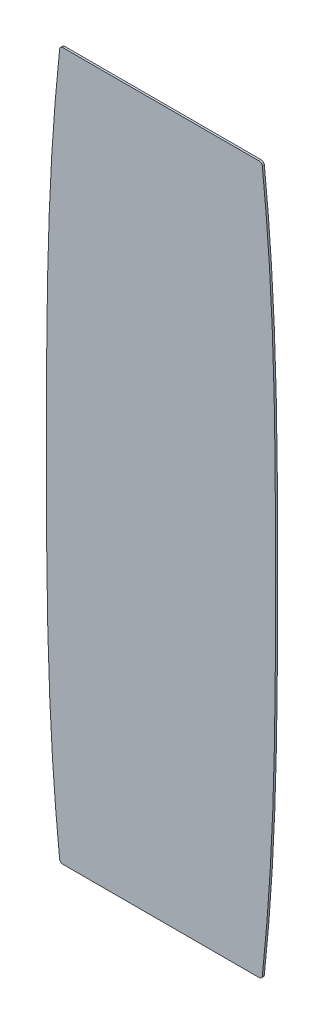
SolidWorks part; units mm, degrees
ref_plane "Front" through (0, 0, 0) normal (0, 0, 1) x (1, 0, 0)
ref_plane "Top" through (0, 0, 0) normal (0, 1, 0) x (1, 0, 0)
ref_plane "Right" through (0, 0, 0) normal (1, 0, 0) x (0, 0, -1)
sketch "Sketch1" plane through (0, 0, 0) normal (0, 0, 1) x (1, 0, 0)
  line L4 (-23.7959, -85.8) -> (23.7959, -85.8)
  line L5 (23.7959, 85.8) -> (-23.7959, 85.8)
  line L6 (-23.7959, -85.8) -> (23.7959, -85.8)
  line L7 (23.7959, 85.8) -> (-23.7959, 85.8)
  arc A8 (-24.5914, -85.0845) -> (-23.7959, -85.8) centre (-23.7959, -85) ccw
  arc A9 (23.7959, -85.8) -> (24.5914, -85.0845) centre (23.7959, -85) ccw
  arc A10 (24.5914, 85.0845) -> (23.7959, 85.8) centre (23.7959, 85) ccw
  arc A11 (-23.7959, 85.8) -> (-24.5914, 85.0845) centre (-23.7959, 85) ccw
  arc A12 (-24.5914, -85.0845) -> (-23.7959, -85.8) centre (-23.7959, -85) ccw
  arc A13 (23.7959, -85.8) -> (24.5914, -85.0845) centre (23.7959, -85) ccw
  arc A14 (24.5914, 85.0845) -> (23.7959, 85.8) centre (23.7959, 85) ccw
  arc A15 (-23.7959, 85.8) -> (-24.5914, 85.0845) centre (-23.7959, 85) ccw
  spline S8 degree 3 poles (-3802.0274, 987.7222) (80.8283, 660.6198) (-30.7141, 319.4581) (-27.6629, -28.4006) (-27.5516, -35.4997) (-27.1348, -49.6946) (-26.8273, -56.7856) (-26.1559, -67.4085) (-25.8975, -70.9473) (20.9467, -627.9264) (1017.3382, -1119.8071) (3591.242, -1509.4446) knots -11.748468 -11.748468 -11.748468 -11.748468 0.25 0.25 0.5 0.5 0.75 0.75 0.875 0.875 20.43848 20.43848 20.43848 20.43848 only from (-27.8, 0) to (-24.5914, -85.0845)
  spline S9 degree 3 poles (-3801.4835, -888.3345) (-433.1565, -789.8527) (2.3276, -444.1958) (26.8287, -56.7783) (27.1351, -49.686) (27.5518, -35.4924) (27.663, -28.3946) (30.7149, 319.6689) (-80.9395, 661.8598) (3808.3413, 961.2743) knots -13.168575 -13.168575 -13.168575 -13.168575 0.25 0.25 0.5 0.5 0.75 0.75 12.758606 12.758606 12.758606 12.758606 only from (24.5914, -85.0845) to (27.8, 0)
  spline S10 degree 3 poles (3802.0274, -987.7222) (-80.8283, -660.6198) (30.7141, -319.4581) (27.6629, 28.4006) (27.5516, 35.4997) (27.1348, 49.6946) (26.8273, 56.7856) (26.1559, 67.4085) (25.8975, 70.9473) (-20.9467, 627.9264) (-1017.3382, 1119.8071) (-3591.242, 1509.4446) knots -11.748468 -11.748468 -11.748468 -11.748468 0.25 0.25 0.5 0.5 0.75 0.75 0.875 0.875 20.43848 20.43848 20.43848 20.43848 only from (27.8, 0) to (24.5914, 85.0845)
  spline S11 degree 3 poles (3801.4835, 888.3345) (433.1565, 789.8527) (-2.3276, 444.1958) (-26.8287, 56.7783) (-27.1351, 49.686) (-27.5518, 35.4924) (-27.663, 28.3946) (-30.7149, -319.6689) (80.9395, -661.8598) (-3808.3413, -961.2743) knots -13.168575 -13.168575 -13.168575 -13.168575 0.25 0.25 0.5 0.5 0.75 0.75 12.758606 12.758606 12.758606 12.758606 only from (-24.5914, 85.0845) to (-27.8, 0)
  spline S12 degree 3 poles (-27.8, 0) (-27.8, -7.1003) (-27.7874, -14.2005) (-27.6629, -28.4006) (-27.5516, -35.4997) (-27.1348, -49.6946) (-26.8273, -56.7856) (-26.1559, -67.4085) (-25.8975, -70.9473) (-25.3027, -78.0197) (-24.9665, -81.5533) (-24.5914, -85.0845) knots 0 0 0 0 0.25 0.25 0.5 0.5 0.75 0.75 0.875 0.875 1 1 1 1
  spline S13 degree 3 poles (24.5914, -85.0845) (25.3415, -78.024) (25.9324, -70.9502) (26.8287, -56.7783) (27.1351, -49.686) (27.5518, -35.4924) (27.663, -28.3946) (27.7874, -14.1979) (27.8, -7.099) (27.8, 0) knots 0 0 0 0 0.25 0.25 0.5 0.5 0.75 0.75 1 1 1 1
  spline S14 degree 3 poles (27.8, 0) (27.8, 7.1003) (27.7874, 14.2005) (27.6629, 28.4006) (27.5516, 35.4997) (27.1348, 49.6946) (26.8273, 56.7856) (26.1559, 67.4085) (25.8975, 70.9473) (25.3027, 78.0197) (24.9665, 81.5533) (24.5914, 85.0845) knots 0 0 0 0 0.25 0.25 0.5 0.5 0.75 0.75 0.875 0.875 1 1 1 1
  spline S15 degree 3 poles (-24.5914, 85.0845) (-25.3415, 78.024) (-25.9324, 70.9502) (-26.8287, 56.7783) (-27.1351, 49.686) (-27.5518, 35.4924) (-27.663, 28.3946) (-27.7874, 14.1979) (-27.8, 7.099) (-27.8, 0) knots 0 0 0 0 0.25 0.25 0.5 0.5 0.75 0.75 1 1 1 1
  dimension "D1" = 0.2
extrude "Boss-Extrude1" add sketch "Sketch1" along normal up to surface (0.5 mm away)
